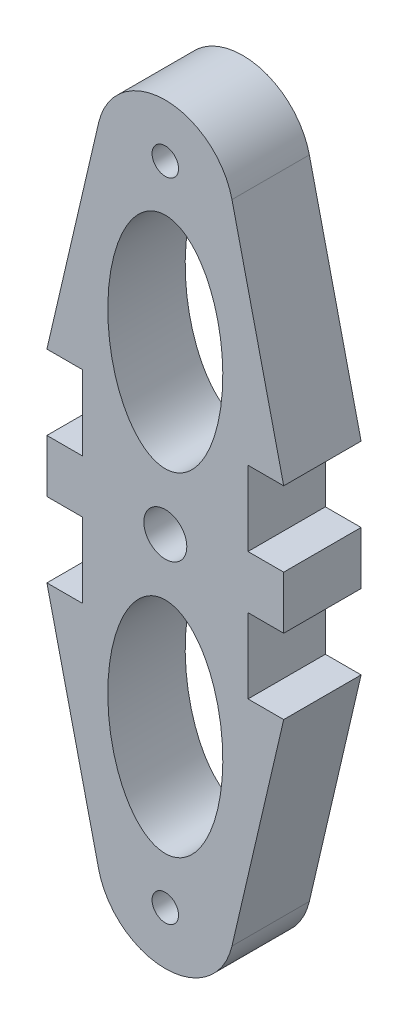
SolidWorks part; units mm, degrees
material "Acrylic (Medium-high impact)"
ref_plane "Front Plane" through (0, 0, 0) normal (0, 0, 1) x (1, 0, 0)
ref_plane "Top Plane" through (0, 0, 0) normal (0, 1, 0) x (1, 0, 0)
ref_plane "Right Plane" through (0, 0, 0) normal (1, 0, 0) x (0, 0, -1)
sketch "Sketch1" plane through (0, 0, 0) normal (0, 0, 1) x (1, 0, 0)
  line L0 (-213.0435, 465.4025) -> (49786.9565, 465.4025) construction
  line L1 (781.4092, 465.4025) -> (778.7092, 465.4025)
  line L2 (781.4092, 465.4025) -> (781.4092, 471.0525)
  line L3 (781.4092, 471.0525) -> (778.7092, 471.0525)
  line L4 (787.6592, -515.9253) -> (787.6592, 49484.0747) construction
  line L5 (-215.2235, 463.4024) -> (49784.7765, 463.4024) construction
  line L6 (793.9092, 471.0525) -> (793.9092, 487.8374) construction
  line L7 (-217.5077, 461.4022) -> (49782.4923, 461.4022) construction
  line L8 (785.6592, -537.0976) -> (785.6592, 49462.9024) construction
  line L9 (789.6592, -536.5976) -> (789.6592, 49463.4024) construction
  line L10 (793.9092, 465.4025) -> (796.6092, 465.4025)
  line L11 (781.4092, 471.0525) -> (793.9092, 471.0525) construction
  line L12 (793.9092, 471.0525) -> (796.6092, 471.0525)
  line L13 (793.9092, 465.4025) -> (793.9092, 471.0525)
  line L14 (778.7092, 465.4025) -> (778.7092, 461.4022)
  line L15 (796.6092, 465.4025) -> (796.6092, 461.4022)
  line L16 (786.6592, 487.8374) -> (782.6202, 487.8374) construction
  line L17 (781.4092, 461.4022) -> (778.7092, 461.4022)
  line L19 (781.4092, 455.7522) -> (778.7092, 455.7522)
  line L20 (781.4092, 461.4022) -> (781.4092, 455.7522)
  line L21 (793.9092, 461.4022) -> (796.6092, 461.4022)
  line L22 (793.9092, 461.4022) -> (793.9092, 455.7522)
  line L23 (793.9092, 455.7522) -> (796.6092, 455.7522)
  line L24 (778.7092, 471.0525) -> (782.6202, 487.8374)
  line L25 (792.6982, 487.8374) -> (796.6092, 471.0525)
  line L26 (792.6982, 438.9674) -> (796.6092, 455.7522)
  line L27 (788.6592, 438.9674) -> (792.6982, 438.9674) construction
  line L28 (786.6592, 438.9674) -> (782.6202, 438.9674) construction
  line L29 (778.7092, 455.7522) -> (782.6202, 438.9674)
  line L35 (788.6592, 487.8374) -> (792.6982, 487.8374) construction
  arc A0 (782.6202, 487.8374) -> (792.6982, 487.8374) centre (787.6592, 486.6632) cw
  arc A1 (782.6202, 438.9674) -> (792.6982, 438.9674) centre (787.6592, 440.1415) ccw
  circle A3 centre (787.6592, 487.8374) radius 1
  circle A5 centre (787.6592, 438.9674) radius 1
  circle A6 centre (787.6592, 463.4024) radius 1.625
  ellipse E0 centre (787.6592, 475.9983) end of major axis (787.6592, 467.6962) minor radius 4.3465
  ellipse E1 centre (787.6592, 450.8064) end of major axis (787.6592, 442.5043) minor radius 4.3465
  point P10 (778.7092, 463.4024)
  point P19 (796.6092, 463.4024)
  dimension "D3" = 5.65
  dimension "D10" = 5.174
  dimension "D9" = 2
  dimension "D2" = 2.7
  dimension "D4" = 24.435
  dimension "D5" = 12.5
  dimension "D6" = 16.6042
  dimension "D7" = 8.693
  dimension "D8" = 2.2937
extrude "Boss-Extrude1" add sketch "Sketch1" along normal blind 5.85 contours L3 A3 A5 region at (782.0054, 468.2275, 0)
